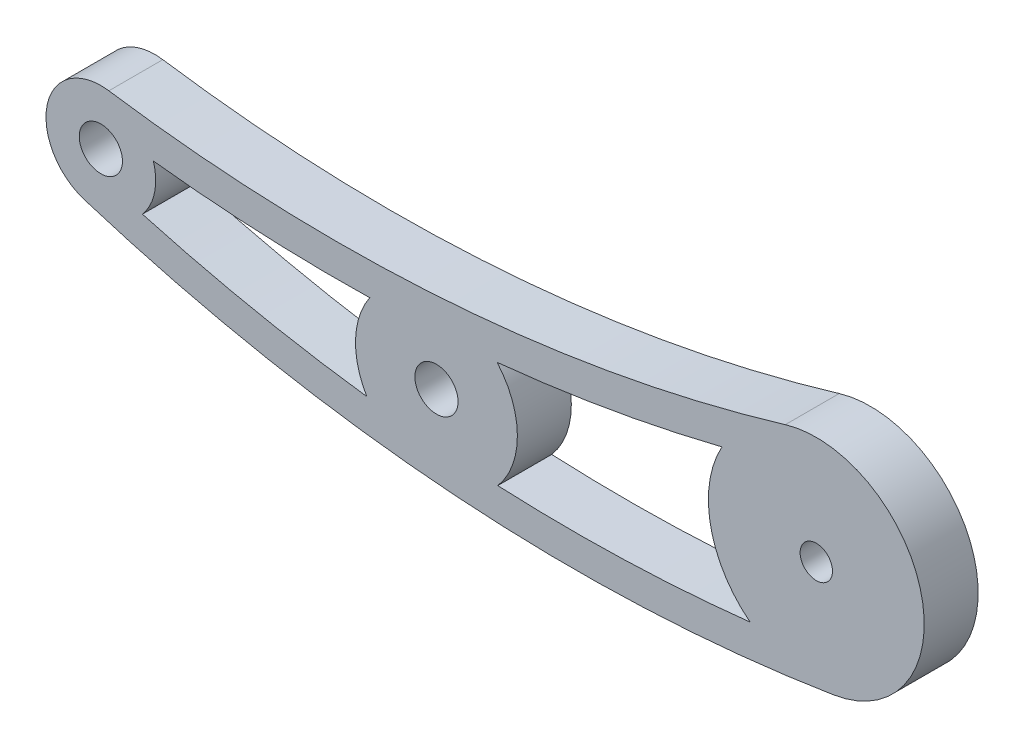
SolidWorks part; units mm, degrees
material "1060 Alloy"
ref_plane "Front Plane" through (0, 0, 0) normal (0, 0, 1) x (1, 0, 0)
ref_plane "Top Plane" through (0, 0, 0) normal (0, 1, 0) x (1, 0, 0)
ref_plane "Right Plane" through (0, 0, 0) normal (1, 0, 0) x (0, 0, -1)
sketch "Sketch1" plane through (0, 0, 0) normal (0, 0, 1) x (1, 0, 0)
  line L0 (0, 0) -> (66.3, 0)
  line L1 (0, -8) -> (66.3, -8)
  line L2 (0, 8) -> (66.3, 8)
  line L3 (0, -5) -> (66.3, -5)
  circle A0 centre (66.3, 0) radius 1.5
  circle A1 centre (0, 0) radius 2
  arc A2 (0, -8) -> (0, 8) centre (0, 0) cw
  arc A3 (66.3, -8) -> (66.3, 8) centre (66.3, 0) ccw
  circle A4 centre (31.1, -3.74) radius 2
  circle A5 centre (33.15, 176.6537) radius 184.6537
  circle A6 centre (33.15, 176.6537) radius 174.6537
  circle A7 centre (0, 0) radius 5.0835
  circle A8 centre (66.3, 0) radius 5.0835
  dimension "D2" = 3
  dimension "D1" = 4
extrude "Extrude1" add sketch "Sketch1" along normal blind 5 contours A7 A5 L3 A1 | A8 L0 A7 L3 A4 | A8 A6 A7 L0 | A8 L3 A5 A0 | A8 L3 A4 A7 A5 | A5 A7 L3 | L3 A8 A5 region at (3.7955, -3.1624, 0) region at (33.15, 1.5509, 0) region at (33.2303, -2.5109, 0) region at (62.4982, 3.1548, 0) region at (0.4491, -5.0241, 0) region at (33.175, -6.2124, 0) region at (65.8509, -5.0241, 0)
sketch "Sketch2" plane through (0, 0, 5) normal (0, 0, 1) x (1, 0, 0)
  circle A0 centre (31.1, -3.74) radius 7.5 construction
  arc A1 (67.8926, -9.8724) -> (63.4272, 9.5785) centre (66.3, 0) ccw
  arc A2 (0.742, 5.029) -> (63.4272, 9.5785) centre (21.8615, 148.164) ccw
  arc A3 (0.9376, 4.9963) -> (-2.1931, -4.5861) centre (0, 0) ccw construction
  arc A4 (67.8926, -9.8724) -> (-1.5236, -4.8498) centre (43.8061, 139.438) cw
  arc A6 (0.742, 5.029) -> (-1.5236, -4.8498) centre (0, 0) ccw
  arc M1 (-2.1931, -4.5861) -> (68.4931, -4.5861) centre (33.15, 176.6537) ccw
  arc M2 (68.4931, -4.5861) -> (65.3624, 4.9963) centre (66.3, 0) ccw
  arc M3 (65.3624, 4.9963) -> (0.9376, 4.9963) centre (33.15, 176.6537) cw
  arc M4 (0.9376, 4.9963) -> (-2.1931, -4.5861) centre (0, 0) ccw
  circle M5 centre (31.1, -3.74) radius 2
  circle M6 centre (0, 0) radius 2
  circle M7 centre (66.3, 0) radius 1.5
  dimension "D1" = 15
  dimension "D2" = 20
extrude "Boss-Extrude1" add sketch "Sketch2" against normal blind 5 contours M4 M1 M2 M3 M5 M7 M6 | A6 A4 A1 A2 M1 M4 M3 M2 region at (32.9504, -10.5958, 5) region at (33.4408, -1.7674, 5)
sketch "Sketch3" plane through (0, 0, 5) normal (0, 0, 1) x (1, 0, 0)
  arc A4 (3.8522, -3.317) -> (4.8693, 1.4601) centre (0, 0) ccw
  arc A5 (24.9211, 0.511) -> (24.6452, -7.5591) centre (31.1, -3.74) ccw
  arc A6 (57.5597, 4.8587) -> (60.1654, -7.8972) centre (66.3, 0) ccw
  arc A7 (36.7182, 1.2285) -> (57.5597, 4.8587) centre (21.8615, 148.164) ccw
  arc A8 (0.3041, 2.0612) -> (-0.6245, -1.9877) centre (0, 0) ccw
  arc A9 (-0.6245, -1.9877) -> (67.4148, -6.9107) centre (43.8061, 139.438) ccw
  arc A10 (67.4148, -6.9107) -> (64.289, 6.7049) centre (66.3, 0) ccw
  arc A11 (0.3041, 2.0612) -> (64.289, 6.7049) centre (21.8615, 148.164) ccw
  arc A12 (0.3041, 2.0612) -> (-0.6245, -1.9877) centre (0, 0) ccw
  arc A13 (3.8522, -3.317) -> (24.6452, -7.5591) centre (43.8061, 139.438) ccw
  arc A15 (4.8693, 1.4601) -> (24.9211, 0.511) centre (21.8615, 148.164) ccw
  arc A16 (36.7813, -8.6361) -> (60.1654, -7.8972) centre (43.8061, 139.438) ccw
  arc A17 (36.7813, -8.6361) -> (36.7182, 1.2285) centre (31.1, -3.74) ccw
  dimension "D1" = 3
extrude "Cut-Extrude1" cut sketch "Sketch3" against normal blind 5 contours A15 A4 A13 A5 | A17 A16 A6 A7 region at (15.0924, -2.5798, 5) region at (48.0374, -3.0102, 5)
move or copy body "Body-Move/Copy1" [suppressed] bodies to move or copy 105
move or copy body "Body-Move/Copy2" [suppressed] bodies to move or copy 105
